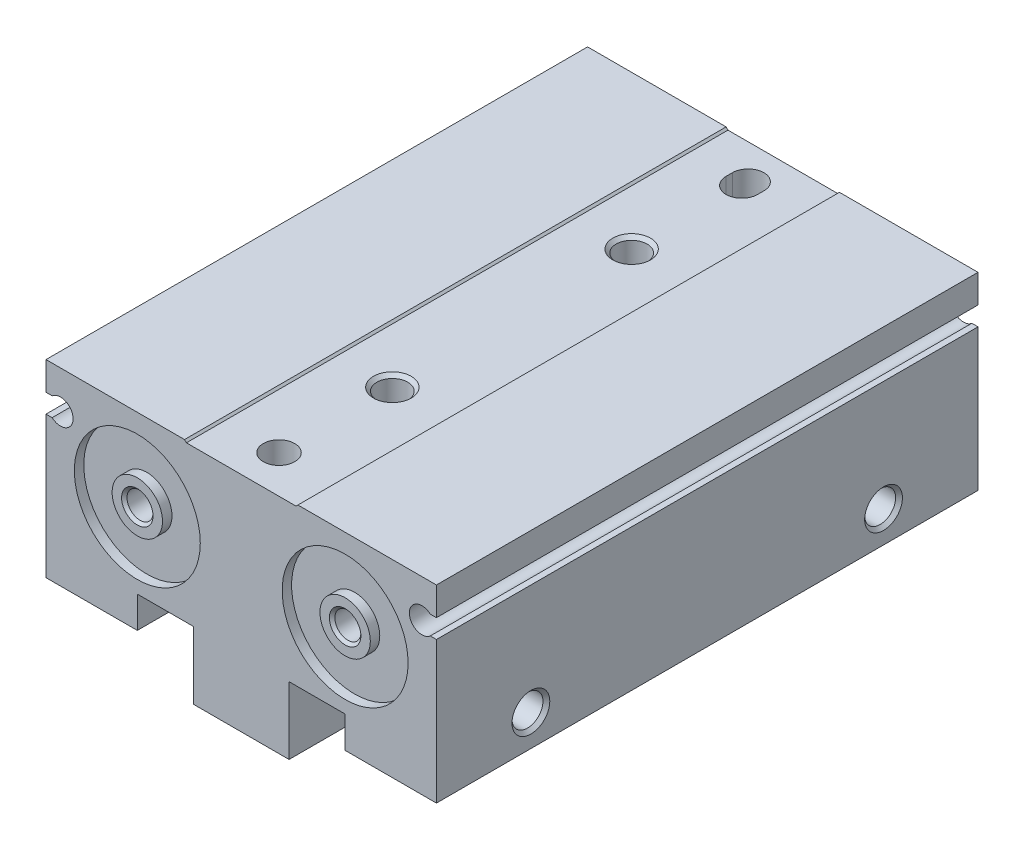
SolidWorks part; units mm, degrees
ref_plane "前视基准面" through (0, 0, 0) normal (0, 0, 1) x (1, 0, 0)
ref_plane "上视基准面" through (0, 0, 0) normal (0, 1, 0) x (1, 0, 0)
ref_plane "右视基准面" through (0, 0, 0) normal (1, 0, 0) x (0, 0, -1)
ref_plane "基准面4" through (0, 0, 0) normal (0, 0, 1) x (1, 0, 0)
sketch "草图1" plane through (0, 0, 0) normal (0, 0, 1) x (1, 0, 0)
  line L0 (-31, -30) -> (-16.5, -30)
  line L1 (-16.5, -30) -> (-16.5, -25)
  line L2 (-16.5, -25) -> (-7.6, -25)
  line L3 (-7.6, -25) -> (-7.6, -35.7)
  line L4 (-7.6, -35.7) -> (7.6, -35.7)
  line L5 (7.6, -35.7) -> (7.6, -25)
  line L6 (7.6, -25) -> (16.5, -25)
  line L7 (16.5, -25) -> (16.5, -30)
  line L8 (16.5, -30) -> (31, -30)
  line L9 (31, -30) -> (31, -7.5)
  line L10 (31, -7.5) -> (30.0229, -7.5)
  line L11 (30.0229, -4.5) -> (31, -4.5)
  line L12 (31, -4.5) -> (31, 0)
  line L13 (31, 0) -> (9, 0)
  line L14 (9, 0) -> (8.7, -0.3)
  line L15 (8.7, -0.3) -> (-8.7, -0.3)
  line L16 (-8.7, -0.3) -> (-9, 0)
  line L17 (-9, 0) -> (-31, 0)
  line L18 (-31, 0) -> (-31, -4.5)
  line L19 (-31, -4.5) -> (-30.0229, -4.5)
  line L20 (-30.0229, -7.5) -> (-31, -7.5)
  line L21 (-31, -7.5) -> (-31, -30)
  arc A0 (30.0229, -7.5) -> (30.0229, -4.5) centre (28.7, -6) cw
  arc A1 (-30.0229, -4.5) -> (-30.0229, -7.5) centre (-28.7, -6) cw
extrude "凸台-拉伸1" add sketch "草图1" against normal blind 43 and the other way blind 43
ref_plane "基准面5" through (0, 0, 0) normal (1, 0, 0) x (0, 0, -1)
sketch "草图2" plane through (0, 0, 0) normal (1, 0, 0) x (0, 0, -1)
  line L0 (19, -0.3) -> (22, -0.3)
  line L1 (22, -0.3) -> (21.4585, -0.8415)
  line L2 (21.4585, -0.8415) -> (21.4585, -15.3)
  line L3 (21.4585, -15.3) -> (21.6, -15.3)
  line L4 (21.6, -15.3) -> (21.6, -25)
  line L5 (21.6, -25) -> (24, -25)
  line L6 (24, -25) -> (24, -35.7)
  line L7 (24, -35.7) -> (19, -35.7)
  line L8 (19, -35.7) -> (19, -0.3)
  line L9 (19, -35.7) -> (19, -0.3) construction
revolve "切除-旋转1" cut sketch "草图2" angle 360 about L9 reverse direction yes
cosmetic thread "装饰螺纹线1" parameters "D1"=15, "D2"=6
ref_plane "基准面6" through (0, 0, 0) normal (1, 0, 0) x (0, 0, -1)
sketch "草图3" plane through (0, 0, 0) normal (1, 0, 0) x (0, 0, -1)
  line L0 (-19, -0.3) -> (-16, -0.3)
  line L1 (-16, -0.3) -> (-16.5415, -0.8415)
  line L2 (-16.5415, -0.8415) -> (-16.5415, -15.3)
  line L3 (-16.5415, -15.3) -> (-16.4, -15.3)
  line L4 (-16.4, -15.3) -> (-16.4, -25)
  line L5 (-16.4, -25) -> (-14, -25)
  line L6 (-14, -25) -> (-14, -35.7)
  line L7 (-14, -35.7) -> (-19, -35.7)
  line L8 (-19, -35.7) -> (-19, -0.3)
  line L9 (-19, -35.7) -> (-19, -0.3) construction
revolve "切除-旋转2" cut sketch "草图3" angle 360 about L9 reverse direction yes
ref_plane "基准面7" through (0, -0.3, 0) normal (0, 1, 0) x (1, 0, 0)
sketch "草图4" plane through (0, -0.3, 0) normal (0, 1, 0) x (1, 0, 0)
  line L0 (-2.5, 37.5) -> (-2.5, 36.5)
  line L1 (2.5, 36.5) -> (2.5, 37.5)
  arc A0 (-2.5, 36.5) -> (2.5, 36.5) centre (0, 36.5) ccw
  arc A1 (2.5, 37.5) -> (-2.5, 37.5) centre (0, 37.5) ccw
extrude "切除-拉伸1" cut sketch "草图4" against normal blind 4
ref_plane "基准面8" through (0, -0.3, 0) normal (0, 1, 0) x (1, 0, 0)
sketch "草图5" plane through (0, -0.3, 0) normal (0, 1, 0) x (1, 0, 0)
  circle A0 centre (0, -37) radius 2.5
extrude "切除-拉伸2" cut sketch "草图5" against normal blind 4
ref_plane "基准面9" through (0, -25, 0) normal (0, 1, 0) x (1, 0, 0)
sketch "草图6" plane through (0, -25, 0) normal (0, 1, 0) x (1, 0, 0)
  line L0 (31, 28) -> (31, 25)
  line L1 (31, 25) -> (30.4585, 25.5415)
  line L2 (30.4585, 25.5415) -> (25, 25.5415)
  line L3 (25, 25.5415) -> (25, 28)
  line L4 (25, 28) -> (31, 28)
  line L5 (25, 28) -> (31, 28) construction
revolve "切除-旋转3" cut sketch "草图6" angle 360 about L5 reverse direction yes
ref_plane "基准面10" through (0, -25, 0) normal (0, 1, 0) x (1, 0, 0)
sketch "草图7" plane through (0, -25, 0) normal (0, 1, 0) x (1, 0, 0)
  line L0 (31, -28) -> (31, -31)
  line L1 (31, -31) -> (30.4585, -30.4585)
  line L2 (30.4585, -30.4585) -> (25, -30.4585)
  line L3 (25, -30.4585) -> (25, -28)
  line L4 (25, -28) -> (31, -28)
  line L5 (25, -28) -> (31, -28) construction
revolve "切除-旋转4" cut sketch "草图7" angle 360 about L5 reverse direction yes
ref_plane "基准面11" through (0, -25, 0) normal (0, 1, 0) x (1, 0, 0)
sketch "草图8" plane through (0, -25, 0) normal (0, 1, 0) x (1, 0, 0)
  line L0 (-25, 28) -> (-25, 25.5415)
  line L1 (-25, 25.5415) -> (-30.4585, 25.5415)
  line L2 (-30.4585, 25.5415) -> (-31, 25)
  line L3 (-31, 25) -> (-31, 28)
  line L4 (-31, 28) -> (-25, 28)
  line L5 (-31, 28) -> (-25, 28) construction
revolve "切除-旋转5" cut sketch "草图8" angle 360 about L5 reverse direction yes
ref_plane "基准面12" through (0, -25, 0) normal (0, 1, 0) x (1, 0, 0)
sketch "草图9" plane through (0, -25, 0) normal (0, 1, 0) x (1, 0, 0)
  line L0 (-25, -28) -> (-25, -30.4585)
  line L1 (-25, -30.4585) -> (-30.4585, -30.4585)
  line L2 (-30.4585, -30.4585) -> (-31, -31)
  line L3 (-31, -31) -> (-31, -28)
  line L4 (-31, -28) -> (-25, -28)
  line L5 (-31, -28) -> (-25, -28) construction
revolve "切除-旋转6" cut sketch "草图9" angle 360 about L5 reverse direction yes
ref_plane "基准面13" through (26, 0, 0) normal (1, 0, 0) x (0, 0, -1)
sketch "草图10" plane through (26, 0, 0) normal (1, 0, 0) x (0, 0, -1)
  line L0 (20, -30) -> (17, -30)
  line L1 (17, -30) -> (17.5415, -29.4585)
  line L2 (17.5415, -29.4585) -> (17.5415, -24)
  line L3 (17.5415, -24) -> (20, -24)
  line L4 (20, -24) -> (20, -30)
  line L5 (20, -24) -> (20, -30) construction
revolve "切除-旋转7" cut sketch "草图10" angle 360 about L5 reverse direction yes
ref_plane "基准面14" through (-26, 0, 0) normal (1, 0, 0) x (0, 0, -1)
sketch "草图11" plane through (-26, 0, 0) normal (1, 0, 0) x (0, 0, -1)
  line L0 (-20, -30) -> (-23, -30)
  line L1 (-23, -30) -> (-22.4585, -29.4585)
  line L2 (-22.4585, -29.4585) -> (-22.4585, -24)
  line L3 (-22.4585, -24) -> (-20, -24)
  line L4 (-20, -24) -> (-20, -30)
  line L5 (-20, -24) -> (-20, -30) construction
revolve "切除-旋转8" cut sketch "草图11" angle 360 about L5 reverse direction yes
ref_plane "基准面15" through (-26, 0, 0) normal (1, 0, 0) x (0, 0, -1)
sketch "草图12" plane through (-26, 0, 0) normal (1, 0, 0) x (0, 0, -1)
  line L0 (20, -30) -> (17, -30)
  line L1 (17, -30) -> (17.5415, -29.4585)
  line L2 (17.5415, -29.4585) -> (17.5415, -24)
  line L3 (17.5415, -24) -> (20, -24)
  line L4 (20, -24) -> (20, -30)
  line L5 (20, -24) -> (20, -30) construction
revolve "切除-旋转9" cut sketch "草图12" angle 360 about L5 reverse direction yes
ref_plane "基准面16" through (26, 0, 0) normal (1, 0, 0) x (0, 0, -1)
sketch "草图13" plane through (26, 0, 0) normal (1, 0, 0) x (0, 0, -1)
  line L0 (-20, -30) -> (-23, -30)
  line L1 (-23, -30) -> (-22.4585, -29.4585)
  line L2 (-22.4585, -29.4585) -> (-22.4585, -24)
  line L3 (-22.4585, -24) -> (-20, -24)
  line L4 (-20, -24) -> (-20, -30)
  line L5 (-20, -24) -> (-20, -30) construction
revolve "切除-旋转10" cut sketch "草图13" angle 360 about L5 reverse direction yes
ref_plane "基准面17" through (0, -25, 0) normal (0, 1, 0) x (1, 0, 0)
sketch "草图14" plane through (0, -25, 0) normal (0, 1, 0) x (1, 0, 0)
  line L0 (-16.5, -9) -> (-16.5, -20)
  line L1 (-16.5, -20) -> (-7.6, -20)
  line L2 (-7.6, -20) -> (-7.6, -9)
  line L3 (-7.6, -9) -> (-16.5, -9)
extrude "切除-拉伸3" cut sketch "草图14" along normal blind 1.6
ref_plane "基准面18" through (0, -25, 0) normal (0, 1, 0) x (1, 0, 0)
sketch "草图15" plane through (0, -25, 0) normal (0, 1, 0) x (1, 0, 0)
  line L0 (7.6, 9) -> (16.5, 9)
  line L1 (16.5, 9) -> (16.5, 20)
  line L2 (16.5, 20) -> (7.6, 20)
  line L3 (7.6, 20) -> (7.6, 9)
extrude "切除-拉伸4" cut sketch "草图15" along normal blind 1.6
ref_plane "基准面19" through (0, 0, 43) normal (0, 0, 1) x (1, 0, 0)
sketch "草图16" plane through (0, 0, 43) normal (0, 0, 1) x (1, 0, 0)
  circle A0 centre (16.5, -13) radius 10
  circle A1 centre (16.5, -13) radius 4
extrude "切除-拉伸5" cut sketch "草图16" against normal blind 1.5
ref_plane "基准面20" through (0, 0, 43) normal (0, 0, 1) x (1, 0, 0)
sketch "草图17" plane through (0, 0, 43) normal (0, 0, 1) x (1, 0, 0)
  circle A0 centre (-16.5, -13) radius 10
  circle A1 centre (-16.5, -13) radius 4
extrude "切除-拉伸6" cut sketch "草图17" against normal blind 1.5
ref_plane "基准面21" through (0, -13, 0) normal (0, 1, 0) x (1, 0, 0)
sketch "草图18" plane through (0, -13, 0) normal (0, 1, 0) x (1, 0, 0)
  line L0 (16.5, -43) -> (14, -43)
  line L1 (14, -43) -> (14.433, -42.567)
  line L2 (14.433, -42.567) -> (14.433, -38)
  line L3 (14.433, -38) -> (16.5, -38)
  line L4 (16.5, -38) -> (16.5, -43)
  line L5 (16.5, -38) -> (16.5, -43) construction
revolve "切除-旋转11" cut sketch "草图18" angle 360 about L5 reverse direction yes
ref_plane "基准面22" through (0, -13, 0) normal (0, 1, 0) x (1, 0, 0)
sketch "草图19" plane through (0, -13, 0) normal (0, 1, 0) x (1, 0, 0)
  line L0 (-16.5, -43) -> (-19, -43)
  line L1 (-19, -43) -> (-18.567, -42.567)
  line L2 (-18.567, -42.567) -> (-18.567, -38)
  line L3 (-18.567, -38) -> (-16.5, -38)
  line L4 (-16.5, -38) -> (-16.5, -43)
  line L5 (-16.5, -38) -> (-16.5, -43) construction
revolve "切除-旋转12" cut sketch "草图19" angle 360 about L5 reverse direction yes
ref_plane "基准面23" through (0, 0, -43) normal (0, 0, 1) x (1, 0, 0)
sketch "草图20" plane through (0, 0, -43) normal (0, 0, 1) x (1, 0, 0)
  circle A0 centre (16.5, -13) radius 10
extrude "切除-拉伸7" cut sketch "草图20" along normal blind 1.5
ref_plane "基准面24" through (0, 0, -43) normal (0, 0, 1) x (1, 0, 0)
sketch "草图21" plane through (0, 0, -43) normal (0, 0, 1) x (1, 0, 0)
  circle A0 centre (-16.5, -13) radius 10
extrude "切除-拉伸8" cut sketch "草图21" along normal blind 1.5
